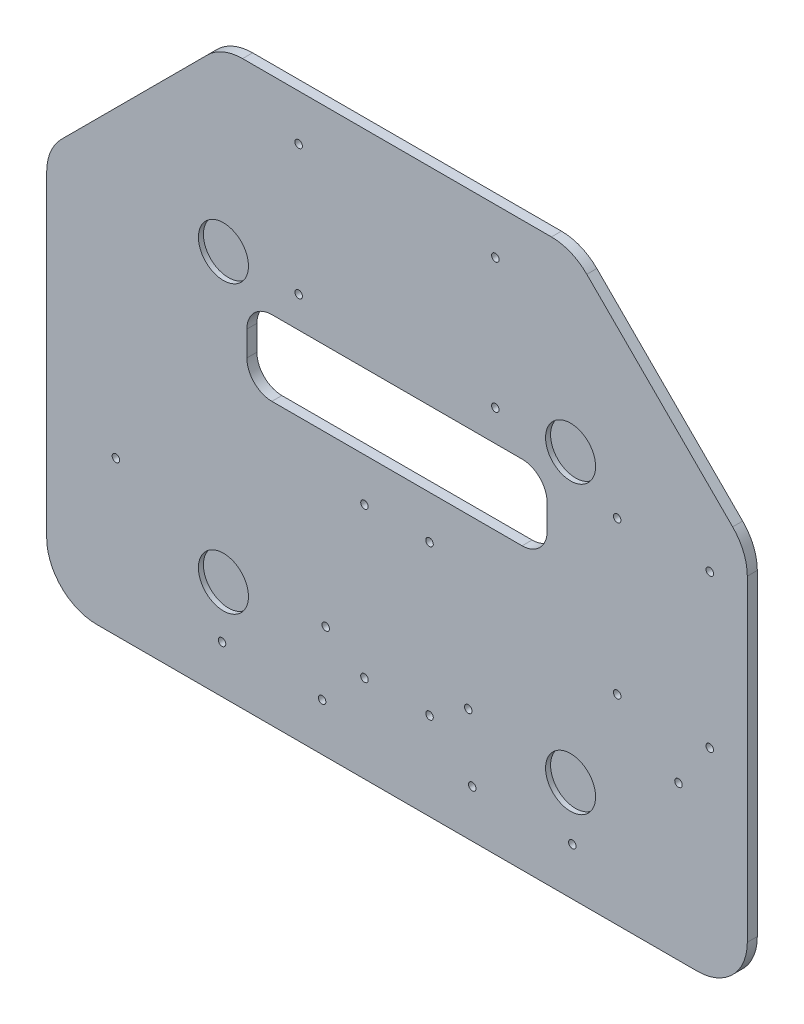
SolidWorks part; units mm, degrees
ref_plane "前视基准面" through (0, 0, 0) normal (0, 0, 1) x (1, 0, 0)
ref_plane "上视基准面" through (0, 0, 0) normal (0, 1, 0) x (1, 0, 0)
ref_plane "右视基准面" through (0, 0, 0) normal (1, 0, 0) x (0, 0, -1)
sketch "草图3" plane through (0, 0, 0) normal (0, 0, 1) x (1, 0, 0)
  line L1 (73.5057, 259.0895) -> (196.9372, 259.0895)
  line L2 (-4.7785, 180.8052) -> (-4.7785, 54.0895)
  line L3 (15.2215, 34.0895) -> (255.2215, 34.0895)
  line L4 (275.2215, 180.8052) -> (275.2215, 54.0895)
  line L6 (1.0793, 194.9474) -> (59.3636, 253.2316)
  line L9 (211.0793, 253.2316) -> (269.3636, 194.9474)
  arc A0 (73.5057, 259.0895) -> (59.3636, 253.2316) centre (73.5057, 239.0895) ccw
  arc A1 (211.0793, 253.2316) -> (196.9372, 259.0895) centre (196.9372, 239.0895) ccw
  arc A2 (1.0793, 194.9474) -> (-4.7785, 180.8052) centre (15.2215, 180.8052) ccw
  arc A3 (-4.7785, 54.0895) -> (15.2215, 34.0895) centre (15.2215, 54.0895) ccw
  arc A4 (255.2215, 34.0895) -> (275.2215, 54.0895) centre (255.2215, 54.0895) ccw
  arc A5 (275.2215, 180.8052) -> (269.3636, 194.9474) centre (255.2215, 180.8052) ccw
  dimension "D1" = 20
  dimension "D2" = 20
  dimension "D3" = 20
extrude "凸台-拉伸1" add sketch "草图3" along normal blind 4
ref_plane "基准面1" through (0, 0, 4) normal (0, 0, 1) x (1, 0, 0)
sketch "草图4" plane through (0, 0, 4) normal (0, 0, 1) x (1, 0, 0)
  line L0 (135.2215, 265.8006) -> (135.2215, 14.6765) construction
  circle A4 centre (95.9215, 240.7454) radius 1.5
  circle A5 centre (174.5215, 240.7454) radius 1.5
  circle A6 centre (174.5215, 188.7454) radius 1.5
  circle A7 centre (95.9215, 188.7454) radius 1.5
  circle A12 centre (105.2937, 53.0683) radius 1.5
  circle A13 centre (165.2937, 53.0683) radius 1.5
sketch "草图6" plane through (0, 0, 4) normal (0, 0, 1) x (1, 0, 0)
  line L0 (135.2215, 265.6507) -> (135.2215, 27.2875) construction
  circle A0 centre (223.2215, 174.8801) radius 1.5
  circle A1 centre (260.2215, 174.8801) radius 1.5
  circle A2 centre (260.2215, 113.8801) radius 1.5
  circle A3 centre (223.2215, 113.8801) radius 1.5
extrude "切除-拉伸3" cut sketch "草图6" against normal blind 4
extrude "切除-拉伸4" cut sketch "草图4" against normal blind 4
sketch "草图7" plane through (0, 0, 4) normal (0, 0, 1) x (1, 0, 0)
  circle A0 centre (122.2215, 129.0895) radius 1.5
  circle A1 centre (148.2215, 129.0895) radius 1.5
  circle A2 centre (122.2215, 69.0895) radius 1.5
  circle A3 centre (148.2215, 69.0895) radius 1.5
extrude "切除-拉伸5" cut sketch "草图7" against normal blind 4
sketch "草图8" plane through (0, 0, 4) normal (0, 0, 1) x (1, 0, 0)
  circle A0 centre (22.8673, 95.4947) radius 1.5
  circle A1 centre (65.2937, 53.0683) radius 1.5
  circle A2 centre (247.7201, 95.4947) radius 1.5
  circle A3 centre (205.2937, 53.0683) radius 1.5
extrude "切除-拉伸6" cut sketch "草图8" against normal blind 4
sketch "草图9" plane through (0, 0, 4) normal (0, 0, 1) x (1, 0, 0)
  line L2 (135.2215, 176.3247) -> (85.2215, 176.3247)
  line L3 (75.2215, 166.3247) -> (75.2215, 156.3247)
  line L4 (85.2215, 146.3247) -> (185.2215, 146.3247)
  line L5 (195.2215, 156.3247) -> (195.2215, 166.3247)
  line L6 (185.2215, 176.3247) -> (135.2215, 176.3247)
  arc A0 (185.2215, 176.3247) -> (195.2215, 166.3247) centre (185.2215, 166.3247) cw
  arc A1 (195.2215, 156.3247) -> (185.2215, 146.3247) centre (185.2215, 156.3247) cw
  arc A2 (85.2215, 146.3247) -> (75.2215, 156.3247) centre (85.2215, 156.3247) cw
  arc A3 (85.2215, 176.3247) -> (75.2215, 166.3247) centre (85.2215, 166.3247) ccw
  dimension "D1" = 10
extrude "切除-拉伸7" cut sketch "草图9" against normal blind 4
sketch "草图10" plane through (0, 0, 4) normal (0, 0, 1) x (1, 0, 0)
  circle A2 centre (106.7215, 79.0895) radius 1.5
  circle A3 centre (163.7215, 79.0895) radius 1.5
extrude "切除-拉伸9" cut sketch "草图10" against normal blind 4
sketch "草图11" plane through (0, 0, 4) normal (0, 0, 1) x (1, 0, 0)
  line L0 (-3.2561, 188.4589) -> (273.6991, 188.4589) construction
  line L1 (65.8521, 257.5671) -> (65.8521, 34.0895) construction
  line L2 (15.2215, 34.0895) -> (255.2215, 34.0895) construction
  line L3 (204.5909, 257.5671) -> (204.5909, 34.0895) construction
  line L4 (-4.7785, 54.0895) -> (275.2215, 54.0895) construction
  arc A0 (1.0793, 194.9474) -> (-4.7785, 180.8052) centre (15.2215, 180.8052) ccw construction
  arc A1 (275.2215, 180.8052) -> (269.3636, 194.9474) centre (255.2215, 180.8052) ccw construction
  arc A2 (73.5057, 259.0895) -> (59.3636, 253.2316) centre (73.5057, 239.0895) ccw construction
  arc A3 (211.0793, 253.2316) -> (196.9372, 259.0895) centre (196.9372, 239.0895) ccw construction
  circle A4 centre (204.5909, 74.0895) radius 10
  circle A5 centre (65.8521, 74.0895) radius 10
  circle A6 centre (65.8521, 188.4589) radius 10
  circle A7 centre (204.5909, 188.4589) radius 10
extrude "切除-拉伸10" cut sketch "草图11" against normal blind 2
